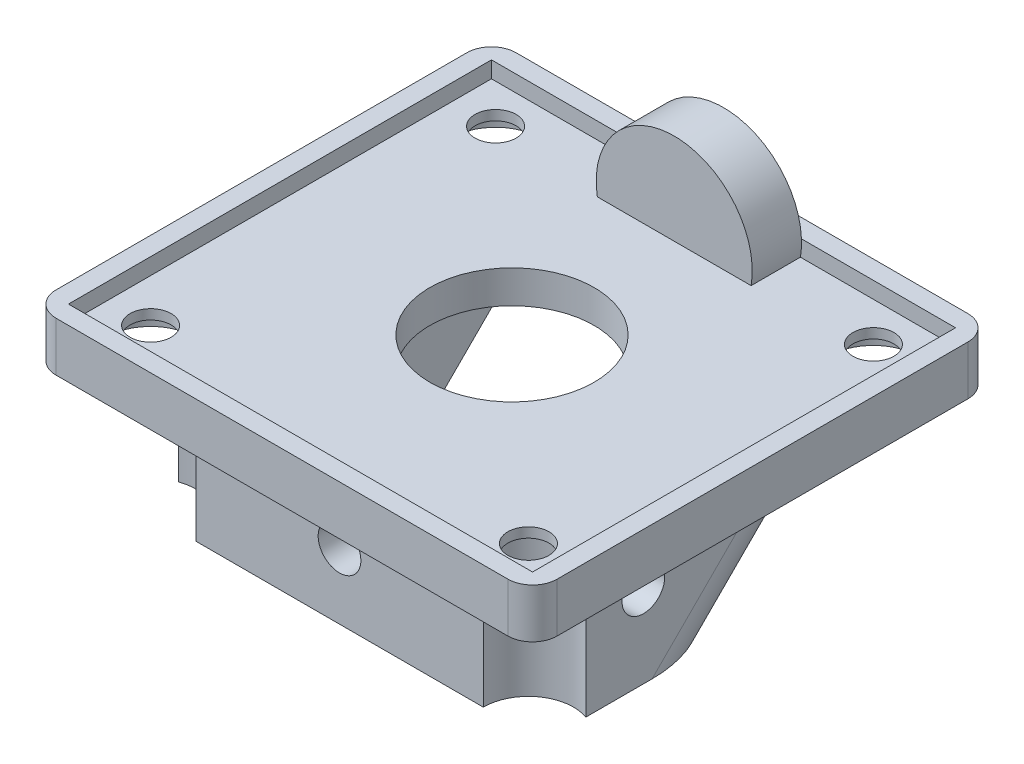
SolidWorks part; units mm, degrees
ref_plane "前视基准面" through (0, 0, 0) normal (0, 0, 1) x (1, 0, 0)
ref_plane "上视基准面" through (0, 0, 0) normal (0, 1, 0) x (1, 0, 0)
ref_plane "右视基准面" through (0, 0, 0) normal (1, 0, 0) x (0, 0, -1)
other "Configuration Table"
sketch "草图1" plane through (0, 0, 0) normal (0, 1, 0) x (1, 0, 0)
  line L1 (0, 0) -> (30.5, 0)
  line L2 (0, 0) -> (0, 28)
  line L3 (0, 28) -> (30.5, 28)
  line L4 (30.5, 0) -> (30.5, 28)
  line L5 (0, 0) -> (30.5, 28) construction
  line L6 (0, 28) -> (30.5, 0) construction
  point P4 (15.25, 14)
  dimension "D1" = 28
  dimension "D2" = 30.5
extrude "凸台-拉伸1" add sketch "草图1" along normal blind 1.6
sketch "草图2" plane through (0, 1.6, 0) normal (0, 1, 0) x (1, 0, 0)
  line L0 (0, 14) -> (30.5, 14) construction
  line L1 (1.125, 26.875) -> (29.375, 26.875)
  line L2 (1.125, 26.875) -> (1.125, 1.125)
  line L3 (1.125, 1.125) -> (29.375, 1.125)
  line L4 (29.375, 26.875) -> (29.375, 1.125)
  line L5 (1.125, 26.875) -> (29.375, 1.125) construction
  line L6 (1.125, 1.125) -> (29.375, 26.875) construction
  line L7 (0, 28) -> (0, 0) construction
  line L8 (30.5, 0) -> (30.5, 28) construction
  line L9 (15.25, 28) -> (15.25, 0) construction
  line L10 (30.5, 28) -> (0, 28) construction
  line L11 (0, 0) -> (30.5, 0) construction
  point P4 (15.25, 14)
  point P17 (16, 14.75)
  dimension "D1" = 28.25
  dimension "D2" = 25.75
extrude "切除-拉伸1" cut sketch "草图2" against normal blind 1
sketch "草图3" plane through (57.75, 0, -26.875) normal (0, 0, 1) x (1, 0, 0)
  line L0 (-42.5, 1.4) -> (-42.5, 0.6) construction
  line L4 (-56.625, 0.6) -> (-28.375, 0.6) construction
  line L5 (-28.375, 1.6) -> (-56.625, 1.6) construction
  line L6 (-47.1821, 0.6) -> (-37.8179, 0.6)
  line L7 (-28.375, 0.6) -> (-56.625, 0.6) construction
  arc A1 (-37.8179, 0.6) -> (-47.1821, 0.6) centre (-42.5, 1.4) ccw
  dimension "D1" = 0.2
  dimension "D2" = 9.5
extrude "凸台-拉伸2" add sketch "草图3" along normal blind 3
sketch "草图5" plane through (0, 0.6, 0) normal (0, 1, 0) x (1, 0, 0)
  line L0 (1.125, 14) -> (29.375, 14) construction
  line L1 (3.75, 24.5) -> (26.75, 24.5) construction
  line L2 (3.75, 24.5) -> (3.75, 3.5) construction
  line L3 (3.75, 3.5) -> (26.75, 3.5) construction
  line L4 (26.75, 24.5) -> (26.75, 3.5) construction
  line L5 (3.75, 24.5) -> (26.75, 3.5) construction
  line L6 (3.75, 3.5) -> (26.75, 24.5) construction
  line L7 (1.125, 26.875) -> (1.125, 1.125) construction
  line L8 (29.375, 1.125) -> (29.375, 26.875) construction
  circle A0 centre (3.75, 24.5) radius 1.25
  circle A1 centre (26.75, 24.5) radius 1.25
  circle A2 centre (3.75, 3.5) radius 1.25
  circle A3 centre (26.75, 3.5) radius 1.25
  point P4 (15.25, 14)
  dimension "D3" = 2.5
  dimension "D1" = 23
  dimension "D2" = 21
extrude "切除-拉伸2" cut sketch "草图5" against normal up to next
sketch "草图6" plane through (0, 0.6, 0) normal (0, 1, 0) x (1, 0, 0)
  line L0 (1.125, 26.875) -> (29.375, 1.125) construction
  line L1 (1.125, 1.125) -> (29.375, 1.125) construction
  circle A0 centre (15.25, 14) radius 5
  point P7 (30.125, 1.875)
  point P8 (16, 14.75)
  dimension "D1" = 10
extrude "切除-拉伸3" cut sketch "草图6" against normal up to next
sketch "草图7" plane through (0, 0, 0) normal (0, -1, 0) x (1, 0, 0)
  line L8 (0, 0) -> (0, -28)
  line L9 (0, -28) -> (30.5, -28)
  line L10 (30.5, -28) -> (30.5, 0)
  line L11 (30.5, 0) -> (0, 0)
  line L12 (0, 0) -> (0, -28)
  line L13 (0, -28) -> (30.5, -28)
  line L14 (30.5, -28) -> (30.5, 0)
  line L15 (30.5, 0) -> (0, 0)
  circle A0 centre (3.75, -3.5) radius 2.75
  circle A1 centre (26.75, -3.5) radius 2.75
  circle A2 centre (3.75, -24.5) radius 2.75
  circle A3 centre (26.75, -24.5) radius 2.75
  circle A4 centre (15.25, -14) radius 5 construction
  circle A5 centre (15.25, -14) radius 5
  dimension "D2" = 5.5
  dimension "D1" = 0
extrude "凸台-拉伸3" add sketch "草图7" along normal blind 1.4
sketch "草图8" plane through (0, -1.4, 0) normal (0, -1, 0) x (1, 0, 0)
  line L0 (22.65, -7) -> (27.65, -7)
  line L1 (2.85, -7) -> (7.85, -7)
  line L2 (2.85, -7) -> (2.85, -21)
  line L3 (2.85, -21) -> (7.85, -21)
  line L4 (27.65, -7) -> (27.65, -21)
  line L5 (2.85, -7) -> (15.25, -14) construction
  line L6 (2.85, -21) -> (15.25, -14) construction
  line L8 (7.85, -7) -> (7.85, -21)
  line L10 (22.65, -7) -> (22.65, -21)
  line L11 (7.85, -7) -> (15.25, -14) construction
  line L12 (7.85, -21) -> (15.25, -14) construction
  line L13 (22.65, -9.8226) -> (27.65, -7) construction
  line L14 (22.65, -18.1774) -> (27.65, -21) construction
  line L15 (22.65, -21) -> (27.65, -21)
  line L16 (15.25, -14) -> (15.25, -9) construction
  circle A0 centre (15.25, -14) radius 5 construction
  point P4 (15.25, -14)
  point P12 (15.25, -14)
  dimension "D1" = 24.8
  dimension "D2" = 14
  dimension "D3" = 5
extrude "凸台-拉伸4" add sketch "草图8" along normal blind 10
sketch "草图9" plane through (2.85, 0, 0) normal (-1, 0, 0) x (0, 0, 1)
  line L0 (-21, -3.9) -> (-13.5, -11.4)
  line L1 (-21, -11.4) -> (-21, -1.4) construction
  line L2 (-7, -11.4) -> (-21, -11.4) construction
  line L3 (-13.5, -11.4) -> (-21, -11.4)
  line L4 (-21, -11.4) -> (-21, -3.9)
  dimension "D1" = 7.5
extrude "切除-拉伸4" cut sketch "草图9" against normal through all
sketch "草图10" plane through (0, 0, -7) normal (0, 0, 1) x (1, 0, 0)
  line L1 (2.85, -11.4) -> (27.65, -11.4)
  line L2 (2.85, -11.4) -> (2.85, -1.4)
  line L3 (2.85, -1.4) -> (27.65, -1.4)
  line L4 (27.65, -11.4) -> (27.65, -1.4)
  line L5 (2.85, -11.4) -> (27.65, -1.4) construction
  line L6 (2.85, -1.4) -> (27.65, -11.4) construction
  point P4 (15.25, -6.4)
extrude "凸台-拉伸5" add sketch "草图10" along normal blind 3.5
sketch "草图11" plane through (0, 0, 0) normal (0, -1, 0) x (1, 0, 0)
  circle A0 centre (3.75, -3.5) radius 2.75 construction
  circle A1 centre (26.75, -3.5) radius 2.75
  circle A2 centre (26.75, -3.5) radius 2.75
  circle A3 centre (3.75, -3.5) radius 2.75
  dimension "D1" = 0
extrude "切除-拉伸5" cut sketch "草图11" along normal through all
sketch "草图12" plane through (2.85, 0, 0) normal (-1, 0, 0) x (0, 0, 1)
  line L0 (0, -1.4) -> (-28, -1.4) construction
  line L2 (-13.5, -11.4) -> (-21, -3.9) construction
  line L3 (-6.0986, -1.4) -> (-6.0986, -11.4) construction
  circle A0 centre (-9.5986, -4.4) radius 1.3
  dimension "D1" = 2.6
  dimension "D2" = 3
  dimension "D3" = 3.5
  dimension "D4" = 7.7085
extrude "切除-拉伸6" cut sketch "草图12" against normal through all
sketch "草图13" plane through (0, 0, -3.5) normal (0, 0, 1) x (1, 0, 0)
  line L0 (15.25, -11.4) -> (15.25, -1.4) construction
  line L1 (6.5, -11.4) -> (24, -11.4) construction
  line L2 (30.5, -1.4) -> (0, -1.4) construction
  circle A0 centre (15.25, -5.4) radius 1.3
  dimension "D1" = 4
  dimension "D2" = 2.6
extrude "切除-拉伸7" cut sketch "草图13" against normal up to next
sketch "草图14" plane through (27.65, 0, 0) normal (1, 0, 0) x (0, 0, -1)
  line L0 (13.5, -11.4) -> (21, -3.9) construction
  line L1 (3.5, -11.4) -> (15.5, -11.4)
  line L2 (3.5, -11.4) -> (3.5, -9.4)
  line L3 (3.5, -9.4) -> (15.5, -9.4)
  line L4 (15.5, -11.4) -> (15.5, -9.4)
  line L5 (3.5, -11.4) -> (15.5, -9.4) construction
  line L6 (3.5, -9.4) -> (15.5, -11.4) construction
  circle A0 centre (9.5986, -4.4) radius 1.3 construction
  point P4 (9.5, -10.4)
  dimension "D1" = 5
extrude "切除-拉伸8" cut sketch "草图14" against normal up to next
sketch "草图15" plane through (0, 0, -7) normal (0, 0, -1) x (-1, 0, 0)
  line L4 (-22.65, -9.4) -> (-7.85, -9.4)
  line L5 (-7.85, -9.4) -> (-7.85, -1.4)
  line L6 (-7.85, -1.4) -> (-22.65, -1.4)
  line L7 (-22.65, -1.4) -> (-22.65, -9.4)
  line L8 (-22.65, -9.4) -> (-7.85, -9.4)
  line L9 (-7.85, -9.4) -> (-7.85, -1.4)
  line L10 (-7.85, -1.4) -> (-22.65, -1.4)
  line L11 (-22.65, -1.4) -> (-22.65, -9.4)
  circle A0 centre (-15.25, -5.4) radius 1.3 construction
  circle A1 centre (-15.25, -5.4) radius 1.3
  dimension "D1" = 0
extrude "凸台-拉伸6" add sketch "草图15" along normal blind 2
fillet "圆角1" radius 3.8 2 edges at (27.65, -6.65, -18.25) (2.85, -6.65, -18.25)
fillet "圆角2" radius 1.5 4 edges at (0, 0.1, -28) (0, 0.1, 0) (30.5, 0.1, -28) (30.5, 0.1, 0)
fillet "圆角3" radius 3 2 edges at (22.65, -2.323, -9) (7.85, -2.323, -9)
sketch "草图16" plane through (22.65, 0, 0) normal (1, 0, 0) x (0, 0, -1)
  line L1 (9, -5.554) -> (9, -3.246)
  line L2 (9, -5.554) -> (9, -3.246)
  arc A1 (9, -3.246) -> (9, -5.554) centre (9.5986, -4.4) ccw
  arc A2 (9, -3.246) -> (9, -5.554) centre (9.5986, -4.4) ccw
  dimension "D1" = 0
extrude "切除-拉伸9" cut sketch "草图16" against normal up to vertex (3 mm away) up to point (19.65, -3.246, -9)
sketch "草图17" plane through (7.85, 0, 0) normal (-1, 0, 0) x (0, 0, 1)
  line L1 (-9, -3.246) -> (-9, -5.554)
  line L2 (-9, -3.246) -> (-9, -5.554)
  arc A1 (-9, -5.554) -> (-9, -3.246) centre (-9.5986, -4.4) ccw
  arc A2 (-9, -5.554) -> (-9, -3.246) centre (-9.5986, -4.4) ccw
  dimension "D1" = 0
extrude "切除-拉伸10" cut sketch "草图17" against normal up to vertex (3 mm away) up to point (10.85, -3.246, -9)
fillet "圆角4" radius 1 2 edges at (10.85, -4.4, -8.2986) (19.65, -4.4, -8.2986)
